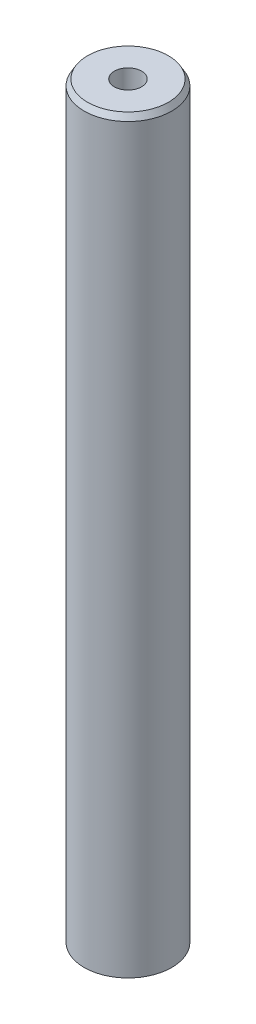
SolidWorks part; units mm, degrees
ref_plane "Front Plane" through (0, 0, 0) normal (0, 0, 1) x (1, 0, 0)
ref_plane "Top Plane" through (0, 0, 0) normal (0, 1, 0) x (1, 0, 0)
ref_plane "Right Plane" through (0, 0, 0) normal (1, 0, 0) x (0, 0, -1)
sketch "Sketch1" plane through (0, 0, 0) normal (0, 1, 0) x (1, 0, 0)
  circle A0 centre (0, 0) radius 35
  dimension "SHAFT_OD" = 70
extrude "Boss-Extrude1" add sketch "Sketch1" along normal blind 600
sketch "Sketch2" plane through (0, 0, 0) normal (0, 1, 0) x (1, 0, 0)
  circle A0 centre (0, 0) radius 10.8831
  dimension "BORE_D" = 21.7662
extrude "Cut-Extrude1" cut sketch "Sketch2" along normal through all
chamfer "Chamfer1" distance 4.723 angle 30 2 edges at (0, 600, 35) (0, 0, 35) first distance on face at (0, 600, 35) first distance on face at (0, 0, 10.8831)
